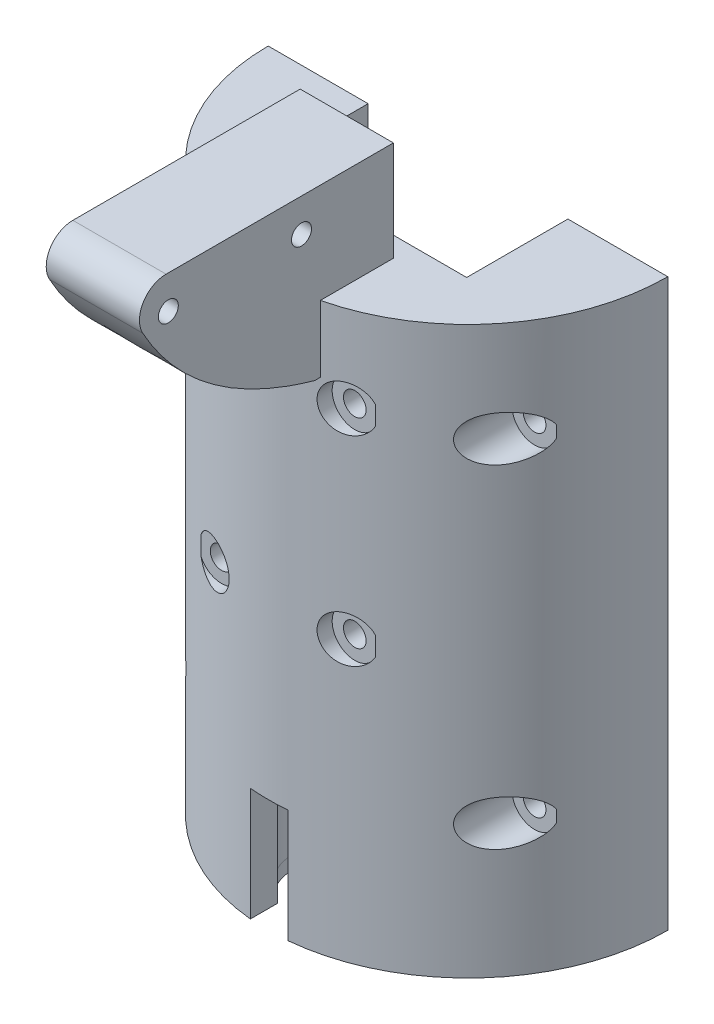
SolidWorks part; units mm, degrees
ref_plane "前视基准面" through (0, 0, 0) normal (0, 0, 1) x (1, 0, 0)
ref_plane "上视基准面" through (0, 0, 0) normal (0, 1, 0) x (1, 0, 0)
ref_plane "右视基准面" through (0, 0, 0) normal (1, 0, 0) x (0, 0, -1)
sketch "草图1" plane through (0, 0, 0) normal (0, 1, 0) x (1, 0, 0)
  line L0 (-30, 0) -> (30, 0)
  line L6 (15, 15.2) -> (-15, 15.2)
  line L7 (15, 15.2) -> (15, -15.2)
  line L8 (15, -15.2) -> (-15, -15.2)
  line L9 (-15, 15.2) -> (-15, -15.2)
  line L10 (15, 15.2) -> (-15, -15.2) construction
  line L11 (15, -15.2) -> (-15, 15.2) construction
  arc A0 (-30, 0) -> (30, 0) centre (0, 0) ccw
  point P0 (0, 0)
  dimension "D3" = 30.4
  dimension "D1" = 30
  dimension "D2" = 60
extrude "凸台-拉伸1" add sketch "草图1" along normal blind 80 contours L0 A0 L8 region at (-22.5, 0, 0.6708)
sketch "草图2" plane through (0, 0, 0) normal (0, 0, 1) x (1, 0, 0)
  line L0 (0, 122.0673) -> (0, -16.729) construction
  line L2 (-30, 0) -> (-15, 0) construction
  circle A0 centre (-10, 37) radius 1.7
  circle A1 centre (-10, 67) radius 1.7
  circle A2 centre (10, 37) radius 1.7
  circle A3 centre (10, 67) radius 1.7
  dimension "D1" = 20
  dimension "D2" = 20
  dimension "D3" = 37
  dimension "D4" = 30
extrude "切除-拉伸1" cut sketch "草图2" along normal blind 100
sketch "草图3" plane through (0, 0, 0) normal (0, 0, -1) x (-1, 0, 0)
  line L0 (-40.9161, 40) -> (57.667, 40) construction
  line L1 (-30, 80) -> (-30, 0) construction
  line L2 (30, 80) -> (30, 0) construction
  line L3 (-30, 0) -> (30, 0) construction
  circle A0 centre (23.5, 65) radius 1.7
  circle A1 centre (-23.5, 65) radius 1.7
  circle A2 centre (23.5, 15) radius 1.7
  circle A3 centre (-23.5, 15) radius 1.7
  dimension "D1" = 50
  dimension "D2" = 50
  dimension "D3" = 6.5
  dimension "D4" = 6.5
  dimension "D5" = 40
extrude "切除-拉伸2" cut sketch "草图3" against normal blind 100
ref_plane "基准面1" through (0, 0, 40) normal (0, 0, -1) x (-1, 0, 0)
sketch "草图4" plane through (0, 0, 40) normal (0, 0, -1) x (-1, 0, 0)
  circle A0 centre (-23.5, 65) radius 3.4
  circle A1 centre (-23.5, 15) radius 3.4
  circle A2 centre (23.5, 65) radius 3.4
  circle A3 centre (23.5, 15) radius 3.4
extrude "切除-拉伸3" cut sketch "草图4" along normal blind 26.5
sketch "草图5" plane through (0, 0, 40) normal (0, 0, -1) x (-1, 0, 0)
  circle A0 centre (-10, 67) radius 3.4
  circle A1 centre (10, 67) radius 3.4
  circle A2 centre (-10, 37) radius 3.4
  circle A3 centre (10, 37) radius 3.4
extrude "切除-拉伸4" cut sketch "草图5" along normal blind 13 contours A2 | A3 | A1 | A0 region at (10, 67, 40) region at (-10, 67, 40) region at (10, 37, 40) region at (-10, 37, 40)
sketch "草图6" plane through (0, 0, 0) normal (0, -1, 0) x (1, 0, 0)
  line L0 (-30, 0) -> (30, 0)
  arc A0 (30, 0) -> (-30, 0) centre (0, 0) ccw
extrude "凸台-拉伸2" add sketch "草图6" along normal blind 3
sketch "草图7" plane through (0, -3, 0) normal (0, -1, 0) x (1, 0, 0)
  line L0 (-30, 0) -> (30, 0) construction
  line L1 (-6, 0) -> (6, 0)
  arc A0 (6, 0) -> (-6, 0) centre (0, 0) ccw
  dimension "D1" = 6
extrude "凸台-拉伸3" add sketch "草图7" along normal blind 9.5
sketch "草图8" plane through (0, 80, 0) normal (0, 1, 0) x (1, 0, 0)
  line L0 (0, 0) -> (0, -36.28) construction
  line L1 (-15, 0) -> (15, 0) construction
  line L2 (-7, -15.2) -> (7, -15.2)
  line L3 (15, -15.2) -> (-15, -15.2) construction
  line L4 (7, -15.2) -> (7, -29.1719)
  line L5 (-7, -15.2) -> (-7, -29.1719)
  arc A0 (-30, 0) -> (30, 0) centre (0, 0) ccw construction
  arc A1 (-7, -29.1719) -> (7, -29.1719) centre (0, 0) ccw
  point P8 (0, -15.2)
  dimension "D1" = 14
ref_plane "基准面2" through (0, 100, 0) normal (0, 1, 0) x (1, 0, 0)
sketch "草图9" plane through (0, 100, 0) normal (0, 1, 0) x (1, 0, 0)
  line L0 (0, 0) -> (0, -36.28) construction
  line L2 (-7, -15.2) -> (7, -15.2)
  line L3 (-7, -15.2) -> (-7, -60.2)
  line L4 (-7, -60.2) -> (7, -60.2)
  line L5 (7, -15.2) -> (7, -60.2)
  dimension "D1" = 14
  dimension "D2" = 45
ref_plane "基准面3" through (0, 70, 0) normal (0, 1, 0) x (1, 0, 0)
sketch "草图10" plane through (0, 70, 0) normal (0, 1, 0) x (1, 0, 0)
  line L0 (-15, 0) -> (15, 0) construction
  line L1 (-7, -29.1719) -> (-7, -15.2)
  line L2 (-7, -15.2) -> (7, -15.2)
  line L3 (7, -15.2) -> (7, -29.1719)
  arc A0 (-7, -29.1719) -> (7, -29.1719) centre (0, 0) ccw
sketch "草图13" plane through (0, 0, 0) normal (1, 0, 0) x (0, 0, -1)
  line L0 (-15.2, 100) -> (-60, 100)
  line L1 (-15.2, 100) -> (-60.2, 100) construction
  line L2 (-15.2, 100) -> (-60.2, 100) construction
  line L3 (-15.2, 100) -> (-15.2, 70)
  line L4 (-15.2, 70) -> (-29.1719, 70) construction
  line L5 (-29.1719, 70) -> (-15.2, 70) construction
  line L6 (-15.2, 70) -> (-30, 70)
  line L7 (-29.1719, 70) -> (-30, 70) construction
  line L8 (-30, 80) -> (-30, -3) construction
  line L9 (0, 80) -> (0, 0) construction
  spline S0 degree 2 poles (-60, 100) (-54.4581, 76.8596) (-30, 70) knots 0 0 0 1 1 1
  dimension "D1" = 15.2
extrude "凸台-拉伸4" add sketch "草图13" along normal mid plane 14
sketch "草图14" plane through (-7, 0, 0) normal (-1, 0, 0) x (0, 0, 1)
  line L0 (0, 80) -> (0, -3) construction
  line L1 (15.2, 100) -> (60, 100) construction
  circle A0 centre (32, 90) radius 1.5
  circle A1 centre (52, 90) radius 1.5
  dimension "D1" = 20
  dimension "D2" = 32
  dimension "D3" = 10
  dimension "D4" = 10
extrude "切除-拉伸6" cut sketch "草图14" against normal blind 14
sketch "草图17" plane through (0, 0, 0) normal (1, 0, 0) x (0, 0, -1)
  line L0 (0, 80) -> (0, -3) construction
  line L1 (-30, -3) -> (0, -3) construction
  circle A0 centre (0, 29) radius 3
  circle A1 centre (0, 49) radius 3
  dimension "D1" = 6
  dimension "D2" = 32
  dimension "D3" = 2
sketch "草图18" plane through (0, 100, 0) normal (0, 1, 0) x (1, 0, 0)
  line L0 (7, -15.2) -> (7, -60) construction
  line L1 (-7, -15.2) -> (7, -15.2)
  line L2 (-7, -15.2) -> (-7, -18.2)
  line L3 (-7, -18.2) -> (7, -18.2)
  line L4 (7, -15.2) -> (7, -18.2)
  dimension "D1" = 3
extrude "切除-拉伸9" cut sketch "草图18" against normal blind 20
sketch "草图19" plane through (0, 0, 0) normal (0, 1, 0) x (1, 0, 0)
  circle A0 centre (0, 0) radius 3
extrude "切除-拉伸10" cut sketch "草图19" against normal blind 3
ref_plane "基准面4" through (0, 26, 0) normal (0, 1, 0) x (1, 0, 0)
fillet "圆角4" radius 1 1 edges at (0, -3, 3)
chamfer "倒角2" distance 2 angle 45 1 edges at (0, 0, 3)
sketch "草图23" plane through (0, -12.5, 0) normal (0, -1, 0) x (1, 0, 0)
  line L0 (0, 8.5053) -> (0, -2.0686) construction
  line L1 (-1.95, 7.9743) -> (1.95, 7.9743)
  line L2 (-1.95, 7.9743) -> (-1.95, 5.6743)
  line L3 (1.95, 7.9743) -> (1.95, 5.6743)
  arc A1 (1.95, 5.6743) -> (-1.95, 5.6743) centre (0, 0) ccw
  point P5 (0, 7.9743)
  dimension "D2" = 6
  dimension "D1" = 3.9
  dimension "D3" = 2.3
extrude "凸台-拉伸5" add sketch "草图23" against normal blind 10
sketch "草图25" plane through (0, -3, 0) normal (0, -1, 0) x (1, 0, 0)
  line L0 (6, 0) -> (30, 0) construction
  circle A0 centre (0, 20.5) radius 6
  dimension "D1" = 12
  dimension "D2" = 20.5
extrude "切除-拉伸14" cut sketch "草图25" against normal blind 15
sketch "草图26" plane through (0, 0, 15.2) normal (0, 0, -1) x (-1, 0, 0)
  line L0 (30, -3) -> (6, -3) construction
  circle A0 centre (0, 9) radius 3
  circle A1 centre (0, 29) radius 3
  circle A2 centre (0, 49) radius 3
  dimension "D1" = 6
  dimension "D2" = 12
  dimension "D3" = 3
sketch "草图27" plane through (0, 100, 0) normal (0, 1, 0) x (1, 0, 0)
  line L1 (-7, -18.2) -> (7, -18.2)
  line L2 (-7, -18.2) -> (-7, -60)
  line L3 (-7, -60) -> (7, -60)
  line L4 (7, -18.2) -> (7, -60)
extrude "切除-拉伸16" cut sketch "草图27" against normal blind 5
fillet "圆角5" radius 4 1 edges at (0, 95, 58.5139)
sketch "草图28" plane through (0, 0, 15.2) normal (0, 0, -1) x (-1, 0, 0)
  line L1 (-2.8125, 12) -> (2.8125, 12)
  line L2 (-2.8125, 12) -> (-2.8125, -3.2908)
  line L3 (-2.8125, -3.2908) -> (2.8125, -3.2908)
  line L4 (2.8125, 12) -> (2.8125, -3.2908)
extrude "切除-拉伸17" cut sketch "草图28" against normal blind 20 contours L4 L3 L2 L1
sketch "草图29" plane through (0, -3, 0) normal (0, -1, 0) x (1, 0, 0)
  line L0 (-30, 0) -> (-6, 0)
  line L1 (2.8125, 29.8679) -> (2.8125, 25.8)
  line L2 (-2.8125, 25.8) -> (-2.8125, 29.8679)
  line L3 (6, 0) -> (30, 0)
  arc A0 (6, 0) -> (-6, 0) centre (0, 0) ccw
  arc A1 (30, 0) -> (2.8125, 29.8679) centre (0, 0) ccw
  arc A2 (-2.8125, 25.8004) -> (2.8125, 25.8004) centre (0, 20.5) ccw
  arc A3 (-2.8125, 29.8679) -> (-30, 0) centre (0, 0) ccw
  arc M3 (-2.8125, 29.8679) -> (-30, 0) centre (0, 0) ccw
  line M4 (-30, 0) -> (-6, 0)
  arc M5 (-6, 0) -> (-1.95, 5.6743) centre (0, 0) cw
  line M6 (-1.95, 5.6743) -> (-1.95, 7.9743)
  line M7 (-1.95, 7.9743) -> (1.95, 7.9743)
  line M8 (1.95, 7.9743) -> (1.95, 5.6743)
  arc M9 (1.95, 5.6743) -> (6, 0) centre (0, 0) cw
  line M10 (6, 0) -> (30, 0)
  arc M11 (30, 0) -> (2.8125, 29.8679) centre (0, 0) ccw
  line M12 (2.8125, 29.8679) -> (2.8125, 25.8)
extrude "凸台-拉伸6" add sketch "草图29" along normal blind 2 contours A2 L2 M3 M4 M5 M6 M7 M8 M9 M10 M11 M12 region at (0, -3, 12.26)
sketch "草图30" plane through (0, -12.5, 0) normal (0, -1, 0) x (1, 0, 0)
  line L0 (0, -3) -> (0, 3) construction
  line L1 (-6, 0) -> (6, 0)
  arc A0 (6, 0) -> (-6, 0) centre (0, 0) ccw
extrude "凸台-拉伸7" add sketch "草图30" along normal blind 2
sketch "草图31" plane through (0, -12.5, 0) normal (0, -1, 0) x (1, 0, 0)
  line L3 (1.95, 5.6743) -> (1.95, 7.9743)
  line L4 (1.95, 7.9743) -> (-1.95, 7.9743)
  line L5 (-1.95, 7.9743) -> (-1.95, 5.6743)
  line L6 (1.95, 5.6743) -> (1.95, 7.9743)
  line L7 (1.95, 7.9743) -> (-1.95, 7.9743)
  line L8 (-1.95, 7.9743) -> (-1.95, 5.6743)
  arc A1 (1.95, 5.6743) -> (-1.95, 5.6743) centre (0, 0) ccw
  arc A2 (1.95, 5.6743) -> (-1.95, 5.6743) centre (0, 0) ccw
  dimension "D1" = 0
extrude "凸台-拉伸8" add sketch "草图31" along normal up to surface (2 mm away) up to face at (0, -14.5, 3)
